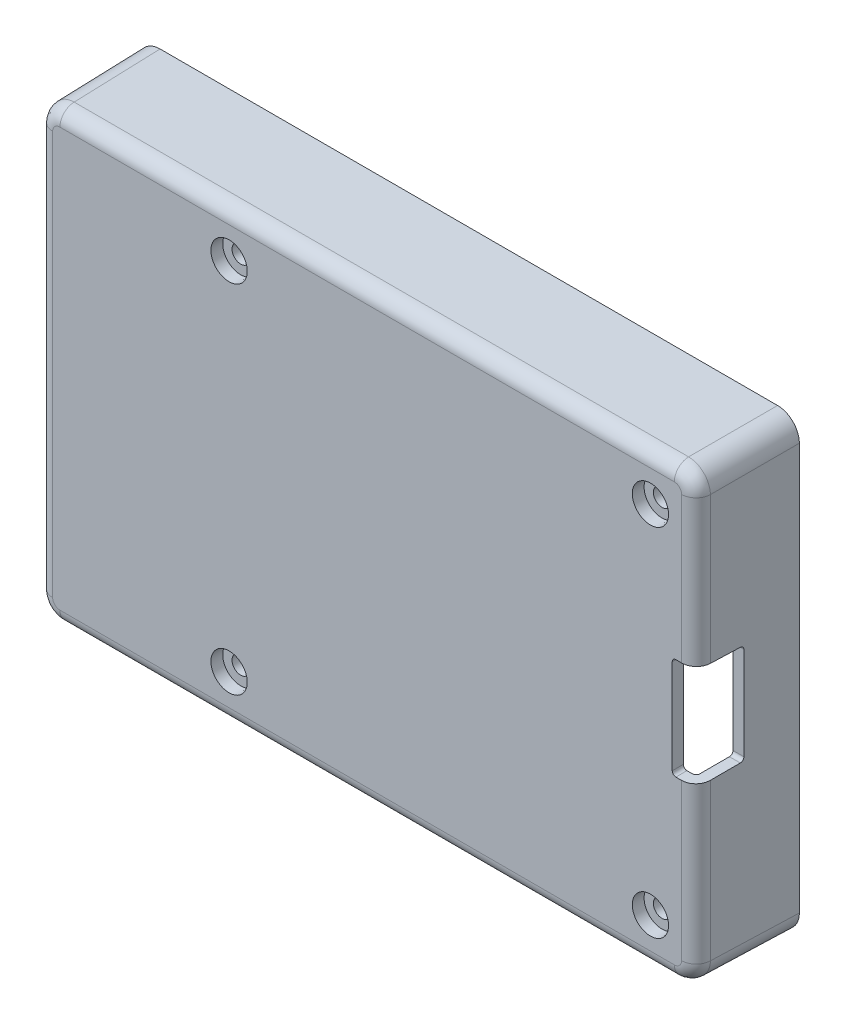
SolidWorks part; units mm, degrees
ref_plane "Front" through (0, 0, 0) normal (0, 0, 1) x (1, 0, 0)
ref_plane "Top" through (0, 0, 0) normal (0, 1, 0) x (1, 0, 0)
ref_plane "Right" through (0, 0, 0) normal (1, 0, 0) x (0, 0, -1)
sketch "Sketch1" plane through (0, 0, 0) normal (0, 0, 1) x (1, 0, 0)
  circle A0 centre (-19, 24.5) radius 3.5
  circle A1 centre (39, 24.5) radius 3.5
  circle A2 centre (39, -24.5) radius 3.5
  circle A3 centre (-19, -24.5) radius 3.5
  dimension "D1" = 7
extrude "Standoffs" add sketch "Sketch1" along normal blind 6 draft 1 draft outward yes
sketch "Sketch2" plane through (0, 0, 6) normal (0, 0, 1) x (1, 0, 0)
  line L0 (40, -28) -> (-40, -28) construction
  line L1 (-45.5, 31) -> (45.5, 31)
  line L2 (-45.5, 31) -> (-45.5, -31)
  line L3 (-45.5, -31) -> (45.5, -31)
  line L4 (45.5, 31) -> (45.5, -31)
  line L5 (-45.5, 31) -> (45.5, -31) construction
  line L6 (-45.5, -31) -> (45.5, 31) construction
  line L7 (42.5, 25.5) -> (42.5, -25.5) construction
  point P0 (0, 0)
  dimension "D1" = 3
  dimension "D2" = 3
extrude "Base" add sketch "Sketch2" against normal blind 1.5
sketch "Sketch3" plane through (0, 0, 4.5) normal (0, 0, -1) x (-1, 0, 0)
  line L0 (-44, 29.5) -> (-44, -29.5)
  line L1 (-44, -29.5) -> (44, -29.5)
  line L2 (44, -29.5) -> (44, 29.5)
  line L3 (44, 29.5) -> (-44, 29.5)
  line L4 (-45.5, 31) -> (-45.5, -31)
  line L5 (-45.5, -31) -> (45.5, -31)
  line L6 (45.5, -31) -> (45.5, 31)
  line L7 (45.5, 31) -> (-45.5, 31)
  line L8 (-45.5, 31) -> (-45.5, -31)
  line L9 (-45.5, -31) -> (45.5, -31)
  line L10 (45.5, -31) -> (45.5, 31)
  line L11 (45.5, 31) -> (-45.5, 31)
  dimension "D1" = 0
  dimension "D2" = 1.5
extrude "Walls " add sketch "Sketch3" along normal blind 12.5
hole_wizard "CBORE for M2 Pan Head Machine Screw1" positions "Sketch4" profile "Sketch5" counterbore size "M2" standard "ANSI Metric" end condition through all
sketch "Sketch4" plane through (0, 0, 6) normal (0, 0, 1) x (1, 0, 0)
  point P0 (39, -24.5)
  point P2 (-19, 24.5)
  point P4 (39, 24.5)
  point P6 (-19, -24.5)
sketch "Sketch5" plane through (39, -24.5, 6) normal (1, 0, 0) x (0, -1, 0)
  line L0 (0, 0) -> (0, 14)
  line L1 (0, 14) -> (1.2, 14)
  line L3 (1.2, 14) -> (1.2, 1.6)
  line L4 (1.2, 1.6) -> (2.5, 1.6)
  line L5 (2.5, 1.6) -> (2.5, 0)
  line L7 (2.5, 0) -> (0, 0)
  line L11 (0, -6.35) -> (0, 107.95) construction
  dimension "Thru Hole Dia." = 2.4
  dimension "Thru Hole Depth" = 14
  dimension "C'Bore Dia." = 5
  dimension "C'Bore Depth" = 1.6
sketch "Sketch7" plane through (0, 0, 0) normal (0, 1, 0) x (1, 0, 0)
  line L0 (10.2, 7.8) -> (10.2, 1.72) construction
  line L1 (12.32, 7.8) -> (8.08, 7.8) construction
  line L2 (15.85, 1.72) -> (4.55, 1.72) construction
  line L3 (40, 1.3) -> (-40, 1.3) construction
  line L4 (18.2, 8.22) -> (2.2, 8.22)
  line L5 (18.2, 8.22) -> (18.2, 1.3)
  line L6 (18.2, 1.3) -> (2.2, 1.3)
  line L7 (2.2, 8.22) -> (2.2, 1.3)
  line L8 (18.2, 8.22) -> (2.2, 1.3) construction
  line L9 (18.2, 1.3) -> (2.2, 8.22) construction
  line L10 (2.7, 6.1) -> (2.7, 5.4) construction
  line L11 (31.75, 4.1294) -> (31.75, 1.44) construction
  line L12 (28.75, 4.1294) -> (34.75, 4.1294) construction
  line L13 (31.635, 1.44) -> (31.865, 1.44) construction
  line L14 (27.51, 4.6294) -> (27.51, 8)
  line L15 (35.99, 0.94) -> (27.51, 0.94)
  line L16 (35.99, 0.94) -> (35.99, 4.6294)
  line L17 (35.99, 4.6294) -> (27.51, 4.6294)
  line L18 (27.51, 0.94) -> (27.51, 4.6294)
  line L19 (35.99, 0.94) -> (27.51, 4.6294) construction
  line L20 (35.99, 4.6294) -> (27.51, 0.94) construction
  line L21 (-45.5, 8) -> (45.5, 8) construction
  line L22 (27.51, 8) -> (35.99, 8)
  line L23 (35.99, 8) -> (35.99, 4.6294)
  line L24 (-14.4, 4.3) -> (-14.4646, 8)
  line L25 (-14.4646, 8) -> (-7.3354, 8)
  line L26 (-7.3354, 8) -> (-7.4, 4.3)
  line L27 (-10.9, 4.3) -> (-10.9, 8) construction
  circle A0 centre (-10.9, 4.3) radius 3.5
  arc A1 (-9.9633, 7.15) -> (-11.8367, 7.15) centre (-10.9, 4.3) ccw construction
  point P12 (10.2, 4.76)
  point P27 (31.75, 2.7847)
  dimension "D1" = 0.5
  dimension "D2" = 0.5
  dimension "D3" = 0.5
  dimension "D4" = 0.5
  dimension "D5" = 1
extrude "Side Ports " cut sketch "Sketch7" against normal through all contours A0 | A0 L26 L25 L24 | L4 L7 L6 L5 | L23 L22 L14 L17 | L18 L15 L16 L17 region at (10.2, 0, -4.76) region at (31.75, 0, -6.3147) region at (31.75, 0, -2.7847) region at (-14.352, 0, -6.1514) region at (-10.9, 0, -4.3)
sketch "Sketch6" plane through (0, 0, 0) normal (1, 0, 0) x (0, 0, -1)
  line L4 (15.8, -8.696) -> (1.6, -8.696)
  line L5 (1.6, -8.696) -> (1.6, -26)
  line L6 (1.6, -26) -> (15.8, -26)
  line L7 (15.8, -26) -> (15.8, -8.696)
  line L8 (15.8, -8.696) -> (1.6, -8.696)
  line L9 (1.6, -8.696) -> (1.6, -26)
  line L10 (1.6, -26) -> (15.8, -26)
  line L11 (15.8, -26) -> (15.8, -8.696)
  line L12 (0.81, -6.14) -> (17.3, -6.14)
  line L13 (0.81, 8.64) -> (0.81, -6.14)
  line L14 (17.3, 8.64) -> (0.81, 8.64)
  line L15 (17.3, -6.14) -> (17.3, 8.64)
  line L16 (0.81, -6.14) -> (17.3, -6.14)
  line L17 (0.81, 8.64) -> (0.81, -6.14)
  line L18 (17.3, 8.64) -> (0.81, 8.64)
  line L19 (17.3, -6.14) -> (17.3, 8.64)
  line L20 (0.81, 11.46) -> (17.3, 11.46)
  line L21 (0.81, 26.24) -> (0.81, 11.46)
  line L22 (17.3, 26.24) -> (0.81, 26.24)
  line L23 (17.3, 11.46) -> (17.3, 26.24)
  line L24 (0.81, 11.46) -> (17.3, 11.46)
  line L25 (0.81, 26.24) -> (0.81, 11.46)
  line L26 (17.3, 26.24) -> (0.81, 26.24)
  line L27 (17.3, 11.46) -> (17.3, 26.24)
  dimension "D1" = 0
  dimension "D2" = 0
  dimension "D3" = 0
extrude "Ethernet Cuts" cut sketch "Sketch6" against normal through all
draft "Draft2" type of draft neutral plane draft angle 1 faces to draft 4 face at (-44, 0.688, -3.84) face at (0, 29.5, -1.75) face at (44, 0, -1.75) face at (7.7625, -29.5, -4.0363) neutral plane through (0, 0, -8) neutral plane normal (0, 0, -1) parameters "D1"=1
draft "Draft1" type of draft neutral plane draft angle 1 faces to draft 4 face at (-45.5, 0.688, -3.6525) face at (0, 31, -1) face at (45.5, 0, -1) face at (7.7625, -31, -3.8488) neutral plane through (0, 0, -8) neutral plane normal (0, 0, -1) reverse direction yes parameters "D1"=1
fillet "Fillet1" radius 3 4 edges at (-45.3778, -30.8778, -1) (45.3778, -30.8778, -1) (45.3778, 30.8778, -1) (-45.3778, 30.8778, -1)
fillet "Fillet2" radius 1.5 4 edges at (-43.8909, -29.3909, -1.75) (-43.8909, 29.3909, -1.75) (43.8909, 29.3909, -1.75) (43.8909, -29.3909, -1.75)
fillet "Fillet3" radius 2 8 edges at (44.3771, 29.8771, 6) (45.2556, 0, 6) (44.3771, -29.8771, 6) (0, -30.7556, 6) (-44.3771, -29.8771, 6) (-45.2556, 0, 6) (-44.3771, 29.8771, 6) (0, 30.7556, 6)
fillet "Fillet4" radius 0.5 12 edges at (-15.4215, 24.5, 4.5) (42.5785, 24.5, 4.5) (42.5785, -24.5, 4.5) (-15.4215, -24.5, 4.5) (43.3426, -28.8426, 4.5) (43.7818, 0, 4.5) (43.3426, 28.8426, 4.5) (0, 29.2818, 4.5) (-43.3426, 28.8426, 4.5) (-43.7818, 0, 4.5) (-43.3426, -28.8426, 4.5) (0, -29.2818, 4.5)
sketch "Sketch8" plane through (0, 0, 0) normal (1, 0, 0) x (0, 0, -1)
  line L0 (-1.3, 0.7) -> (0, 0.7) construction
  line L1 (-1.3, 7.2) -> (-1.3, -5.8) construction
  line L2 (-1.3, 7.2) -> (0, 7.2) construction
  line L3 (-1.8, -6.3) -> (0.5, -6.3)
  line L4 (-1.8, -6.3) -> (-1.8, 7.7)
  line L5 (-1.8, 7.7) -> (0.5, 7.7)
  line L6 (0.5, -6.3) -> (0.5, 7.7)
  line L7 (-1.8, -6.3) -> (0.5, 7.7) construction
  line L8 (-1.8, 7.7) -> (0.5, -6.3) construction
  line L9 (-1.8, -6.3) -> (-6, -6.3)
  line L10 (-6, -30.7556) -> (-6, 30.7556) construction
  line L11 (-6, -6.3) -> (-6, 7.7)
  line L12 (-6, 7.7) -> (-1.8, 7.7)
  point P5 (-0.65, 0.7)
  dimension "D1" = 0.5
  dimension "D2" = 0.5
extrude "SD Card Cut " cut sketch "Sketch8" along normal through all from offset 42 contours L3 L6 L5 L4 | L12 L11 L9 L4 region at (0, 0.7, 0.65) region at (0, 0.7, 3.9)
draft "Draft3" type of draft neutral plane draft angle 1 faces to draft 10 face at (2.2, -30.1915, -4.65) face at (27.51, -30.1884, -4.47) face at (18.2, -30.1915, -4.65) face at (35.99, -30.1884, -4.47) face at (-44.6872, 11.46, -4.405) face at (-44.6872, -6.14, -4.405) face at (-44.6941, -26, -4.8) face at (-44.6872, 8.64, -4.405) face at (-44.6941, -8.696, -4.8) face at (-44.6872, 26.24, -4.405) neutral plane through (0, 0, -8) neutral plane normal (0, 0, -1) parameters "D1"=1
draft "Draft4" type of draft neutral plane draft angle 1 faces to draft 3 face at (42, 0.7, 5.25) face at (43.6752, -6.3, 3.5694) face at (43.6752, 7.7, 3.5694) neutral plane through (-19, 24.5, 6) neutral plane normal (0, 0, 1) parameters "D1"=1
draft "Draft5" type of draft neutral plane draft angle 1 faces to draft 4 face at (41.5, 24.5, 4.4) face at (-16.5, -24.5, 4.4) face at (-16.5, 24.5, 4.4) face at (41.5, -24.5, 4.4) neutral plane through (-19, 24.5, 6) neutral plane normal (0, 0, 1) parameters "D1"=1
fillet "Fillet5" radius 1 4 edges at (27.6332, -30.1268, -0.94) (2.3169, -30.1331, -1.3) (18.0831, -30.1331, -1.3) (35.8668, -30.1268, -0.94)
fillet "Fillet6" radius 0.5 10 edges at (44.6191, -6.1865, -0.5) (42.0131, -6.2869, 5.25) (42.0131, 7.6869, 5.25) (44.6191, 7.5865, -0.5) (-44.6245, 11.5855, -0.81) (-44.6245, -6.0145, -0.81) (-44.6383, -25.8883, -1.6) (-44.6383, -8.8077, -1.6) (-44.6245, 8.5145, -0.81) (-44.6245, 26.1145, -0.81)
